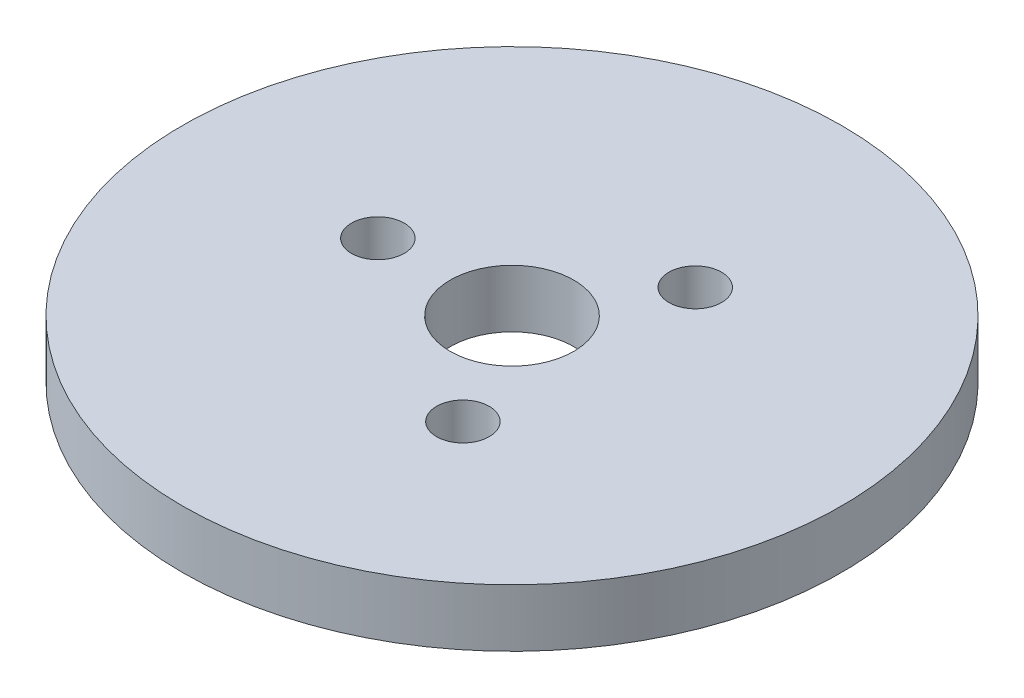
SolidWorks part; units mm, degrees
ref_plane "Front Plane" through (0, 0, 0) normal (0, 0, 1) x (1, 0, 0)
ref_plane "Top Plane" through (0, 0, 0) normal (0, 1, 0) x (1, 0, 0)
ref_plane "Right Plane" through (0, 0, 0) normal (1, 0, 0) x (0, 0, -1)
sketch "Sketch1" plane through (0, 0, 0) normal (0, 1, 0) x (1, 0, 0)
  circle A0 centre (0, 0) radius 80
  dimension "FLANGE_OD" = 160
extrude "Boss-Extrude1" add sketch "Sketch1" along normal blind 14
sketch "Sketch2" plane through (0, 0, 0) normal (0, 1, 0) x (1, 0, 0)
  circle A0 centre (0, 0) radius 15
  dimension "BORE_D" = 30
extrude "Cut-Extrude1" cut sketch "Sketch2" along normal through all
sketch "Sketch3" plane through (0, 14, 0) normal (0, 1, 0) x (1, 0, 0)
  circle A0 centre (0, 0) radius 32.5647 construction
  circle A1 centre (-32.5647, 0) radius 6.3926
  dimension "BOLT_D" = 12.7853
  dimension "BOLT_PCD" = 65.1294
extrude "Cut-Extrude2" cut sketch "Sketch3" against normal blind 13.7267
pattern_circular "CirPattern1" count 3 over 360 about axis through (0, 0, 0) along (0, 1, 0) of "Cut-Extrude2"
